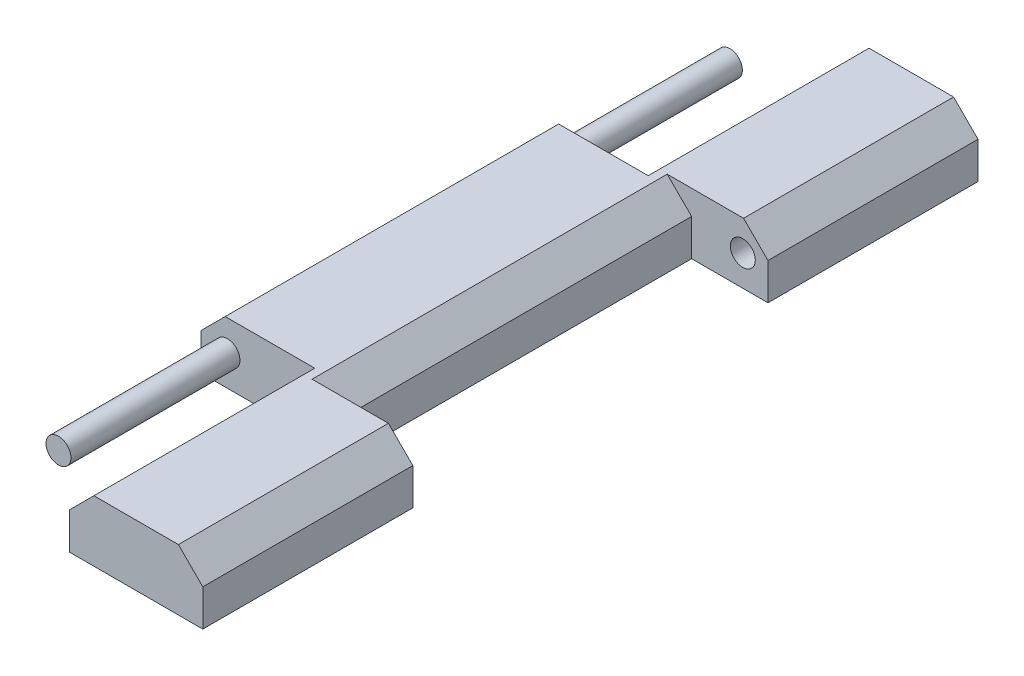
SolidWorks part; units mm, degrees
ref_plane "Front Plane" through (0, 0, 0) normal (0, 0, 1) x (1, 0, 0)
ref_plane "Top Plane" through (0, 0, 0) normal (0, 1, 0) x (1, 0, 0)
ref_plane "Right Plane" through (0, 0, 0) normal (1, 0, 0) x (0, 0, -1)
sketch "Sketch1" plane through (0, 0, 0) normal (0, 1, 0) x (1, 0, 0)
  line L0 (5.4621, -14.5454) -> (5.4621, -31.75)
  line L1 (-5.4621, 31.75) -> (5.4621, 31.75)
  line L2 (-5.4621, 31.75) -> (-5.4621, 13.6578)
  line L3 (-5.4621, -31.75) -> (5.4621, -31.75)
  line L4 (5.4621, 31.75) -> (5.4621, 14.5454)
  line L5 (-5.4621, -13.6578) -> (-5.4621, -31.75)
  line L7 (-12.7958, 13.6578) -> (-5.4621, 13.6578)
  line L8 (-12.7958, 13.6578) -> (-12.7958, -13.6578)
  line L9 (-12.7958, -13.6578) -> (-5.4621, -13.6578)
  line L13 (5.4621, -14.5454) -> (-0.7921, -14.5454)
  line L15 (5.4621, 14.5454) -> (-0.7921, 14.5454)
  line L16 (-0.7921, -14.5454) -> (-0.7921, 14.5454)
  point P0 (0, 0)
  point P6 (-7.9661, -1.326)
  point P12 (5.4621, 0)
  dimension "D1" = 63.5
extrude "Boss-Extrude1" add sketch "Sketch1" along normal blind 5
chamfer "Chamfer1" distance 2 angle 45 6 edges at (5.4621, 5, -23.1477) (-5.4621, 5, -22.7039) (-0.7921, 5, 0) (5.4621, 5, 23.1477) (-5.4621, 5, 22.7039) (-12.7958, 5, 0)
sketch "Sketch3" plane through (5.603, 0, 13.6578) normal (0, 0, 1) x (1, 0, 0)
  circle A0 centre (-16.2147, 2.5) radius 1.0217
ref_plane "Plane1" through (0, 0, 0) normal (0, 0, -1) x (-1, 0, 0)
extrude "Boss-Extrude2" add sketch "Sketch3" along normal mid plane 55 from surface contours A0 starting at plane "Plane1"
pattern_linear "LPattern5" [suppressed] count 14 spacing 20 of bodies 115 101
sketch "Sketch5" plane through (0, 0, -14.5454) normal (0, 0, 1) x (1, 0, 0)
  line L0 (-5.4621, 2.0622) -> (-0.7921, 2.0622)
  line L1 (-5.4621, 3) -> (-5.4621, 0) construction
  line L2 (-0.7921, 3) -> (-0.7921, 0) construction
  line L3 (-10.6117, 2.5) -> (-3.1271, 2.5)
  line L4 (-3.1271, 2.0622) -> (-3.1271, 2.5)
  line L5 (-3.1271, 2.5) -> (3.4003, 2.5)
  circle A0 centre (3.4003, 2.5) radius 1.0217
  circle A1 centre (-10.6117, 2.5) radius 1.0217 construction
extrude "Cut-Extrude1" cut sketch "Sketch5" against normal mid plane 55 from surface contours A0 starting at plane "Plane1"
scale "Scale1" scale about centroid uniform scaling yes scale factor 1.4
